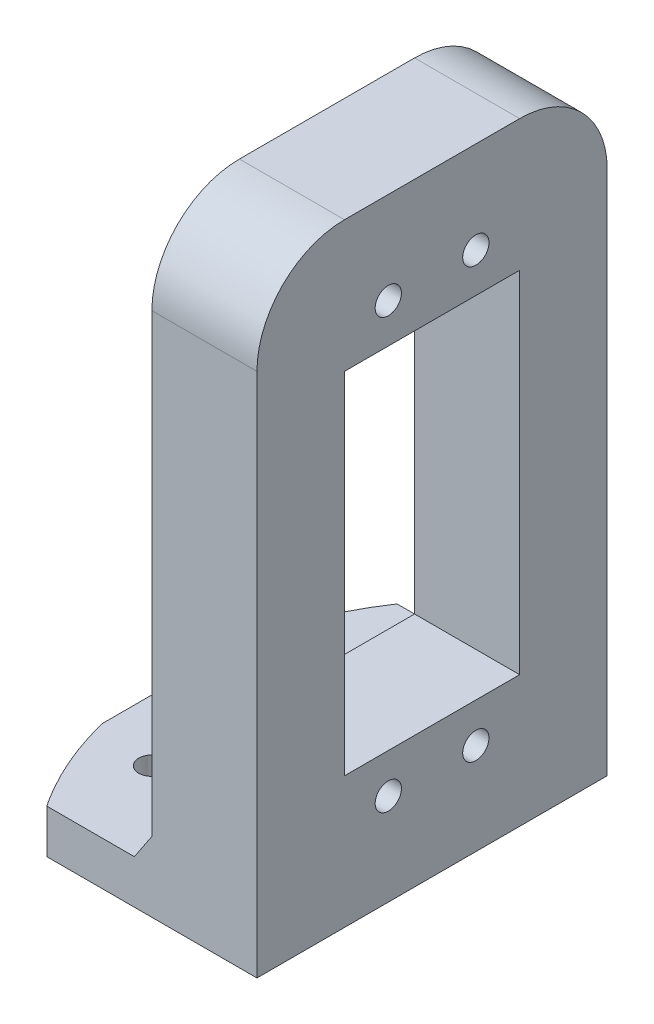
SolidWorks part; units mm, degrees
ref_plane "Front Plane" through (0, 0, 0) normal (0, 0, 1) x (1, 0, 0)
ref_plane "Top Plane" through (0, 0, 0) normal (0, 1, 0) x (1, 0, 0)
ref_plane "Right Plane" through (0, 0, 0) normal (1, 0, 0) x (0, 0, -1)
sketch "Sketch1" plane through (0, 0, 0) normal (1, 0, 0) x (0, 0, -1)
  line L1 (-20, 35) -> (20, 35)
  line L2 (-20, 35) -> (-20, -35)
  line L3 (-20, -35) -> (20, -35)
  line L4 (20, 35) -> (20, -35)
  line L5 (-20, 35) -> (20, -35) construction
  line L6 (-20, -35) -> (20, 35) construction
  point P0 (0, 0)
  dimension "D1" = 40
  dimension "D2" = 70
extrude "Boss-Extrude2" add sketch "Sketch1" along normal blind 9
sketch "Sketch3" plane through (0, 0, 0) normal (-1, 0, 0) x (0, 0, 1)
  line L1 (-10, 20) -> (10, 20)
  line L2 (-10, 20) -> (-10, -20)
  line L3 (-10, -20) -> (10, -20)
  line L4 (10, 20) -> (10, -20)
  line L5 (-10, 20) -> (10, -20) construction
  line L6 (-10, -20) -> (10, 20) construction
  point P0 (0, 0)
  dimension "D1" = 20
  dimension "D2" = 40
extrude "Cut-Extrude1" cut sketch "Sketch3" against normal through all
sketch "Sketch4" plane through (9, 0, 0) normal (1, 0, 0) x (0, 0, -1)
  line L0 (-20, 35) -> (-20, -35) construction
  line L1 (-10, 20) -> (10, 20) construction
  line L2 (10, -20) -> (-10, -20) construction
  circle A0 centre (-5, -24.5) radius 1.5
  circle A1 centre (5, -24.5) radius 1.5
  circle A2 centre (-5, 24.5) radius 1.5
  circle A3 centre (5, 24.5) radius 1.5
  point P0 (-5, 24.5)
  point P3 (5, 24.5)
  point P6 (-5, -24.5)
  point P7 (5, -24.5)
  dimension "D7" = 3
  dimension "D8" = 3
  dimension "D9" = 3
  dimension "D10" = 3
  dimension "D1" = 15
  dimension "D2" = 10
  dimension "D3" = 4.5
  dimension "D4" = 4.5
  dimension "D5" = 4.5
  dimension "D6" = 4.5
extrude "Cut-Extrude2" cut sketch "Sketch4" against normal through all
sketch "Sketch6" plane through (0, 0, 0) normal (-1, 0, 0) x (0, 0, 1)
  line L0 (20, 35) -> (20, -35) construction
  line L1 (-20, -35) -> (20, -35)
  line L2 (-20, -35) -> (-20, -30)
  line L3 (-20, -30) -> (20, -30)
  line L4 (20, -35) -> (20, -30)
  dimension "D1" = 5
extrude "Boss-Extrude3" add sketch "Sketch6" along normal blind 15
sketch "Sketch7" plane through (9, 0, 0) normal (1, 0, 0) x (0, 0, -1)
  line L0 (-20, 35) -> (-20, -35) construction
  line L1 (20, 35) -> (-20, 35) construction
  line L2 (-20, 25) -> (-20, 35)
  line L3 (-20, 35) -> (-10, 35)
  line L4 (20, -35) -> (20, 35) construction
  line L5 (10, 35) -> (20, 35)
  line L6 (20, 35) -> (20, 25)
  arc A0 (-10, 35) -> (-20, 25) centre (-10, 25) ccw
  arc A1 (20, 25) -> (10, 35) centre (10, 25) ccw
  point P0 (-20, 25)
  point P1 (-10, 35)
  point P8 (10, 35)
  point P12 (20, 25)
  dimension "D1" = 10
  dimension "D2" = 10
  dimension "D3" = 10
  dimension "D4" = 10
extrude "Cut-Extrude3" cut sketch "Sketch7" against normal through all
sketch "Sketch8" plane through (0, 0, -20) normal (0, 0, -1) x (-1, 0, 0)
  line L0 (0, -30) -> (0, 25) construction
  line L1 (15, -30) -> (0, -30) construction
  line L2 (0, -27) -> (5, -30)
  line L3 (0, -27) -> (0, -30)
  line L4 (0, -30) -> (5, -30)
  point P0 (0, -27)
  point P1 (5, -30)
  dimension "D1" = 3
  dimension "D2" = 5
extrude "Boss-Extrude4" add sketch "Sketch8" against normal blind 40
sketch "Sketch9" plane through (-15, 0, 0) normal (-1, 0, 0) x (0, 0, 1)
  line L1 (-20, -30) -> (20, -30)
  line L2 (-20, -30) -> (-20, -35)
  line L3 (-20, -35) -> (20, -35)
  line L4 (20, -30) -> (20, -35)
extrude "Boss-Extrude5" add sketch "Sketch9" along normal blind 5
sketch "Sketch10" plane through (0, -30, 0) normal (0, 1, 0) x (1, 0, 0)
  line L0 (-20, -20) -> (-20, 20) construction
  line L1 (-20, 20) -> (-5, 20) construction
  line L2 (-20, -20) -> (-5, -20) construction
  circle A0 centre (-13, 10) radius 1.5
  circle A1 centre (-13, -10) radius 1.5
  point P0 (-13, 10)
  point P1 (-13, -10)
  dimension "D5" = 3
  dimension "D6" = 3
  dimension "D1" = 7
  dimension "D2" = 7
  dimension "D3" = 10
  dimension "D4" = 10
extrude "Cut-Extrude4" cut sketch "Sketch10" against normal through all
sketch "Sketch11" plane through (0, -30, 0) normal (0, 1, 0) x (1, 0, 0)
  line L0 (-20, 20) -> (-5, 20) construction
  line L1 (-20, -20) -> (-20, 20) construction
  line L2 (-20, -20) -> (-5, -20) construction
  line L5 (-15, 20) -> (-23.0603, 8.003) construction
  line L6 (-23.0603, 8.003) -> (-23.0603, -7.997) construction
  line L8 (-23.0603, -7.997) -> (-15, -20) construction
  line L9 (-15, 20) -> (-20, 20)
  line L10 (-20, 20) -> (-20, -20)
  line L11 (-20, -20) -> (-15, -20)
  spline S0 degree 3 poles (-15, 20) (-23.0603, 8.003) (-23.0603, -7.997) (-15, -20) knots 0 0 0 0 1 1 1 1
  point P0 (-15, 20)
  point P1 (-20, 8)
  point P4 (-15, -20)
  point P7 (-20, -8)
  line M3 (-20, -20) -> (-5, -20)
  line M5 (-5, 20) -> (-20, 20)
  line M6 (-20, 20) -> (-20, -20)
  dimension "D1" = 5
  dimension "D2" = 12
  dimension "D3" = 12
  dimension "D4" = 5
extrude "Cut-Extrude5" cut sketch "Sketch11" against normal through all contours S0 M5 M6 | S0 M6 M3 region at (-18.4537, -30, -16.5606) region at (-18.4536, -30, 16.5593)
sketch "Sketch12" plane through (0, 0, 0) normal (-1, 0, 0) x (0, 0, 1)
  line L0 (-20, -27) -> (-20, 25) construction
  line L1 (-10, 35) -> (10, 35)
  line L2 (20, 25) -> (20, -27)
  line L3 (20, -27) -> (-20, -27)
  line L4 (-20, -27) -> (-20, 25)
  line L5 (-10, 20) -> (10, 20)
  line L6 (10, 20) -> (10, -20)
  line L7 (10, -20) -> (-10, -20)
  line L8 (-10, -20) -> (-10, 20)
  arc A0 (-10, 35) -> (-20, 25) centre (-10, 25) ccw construction
  arc A1 (-10, 35) -> (-20, 25) centre (-10, 25) ccw
  arc A2 (20, 25) -> (10, 35) centre (10, 25) ccw
  circle A3 centre (-5, 24.5) radius 1.5
  circle A4 centre (5, 24.5) radius 1.5
  circle A5 centre (5, -24.5) radius 1.5
  circle A6 centre (-5, -24.5) radius 1.5
  spline S0 degree 1 poles (-20, -27) (-20, 25) knots 0 0 1 1
  line M1 (-10, 20) -> (10, 20)
  line M2 (10, 20) -> (10, -20)
  line M3 (10, -20) -> (-10, -20)
  line M4 (-10, -20) -> (-10, 20)
  circle M5 centre (5, -24.5) radius 1.5
  circle M6 centre (-5, 24.5) radius 1.5
  circle M7 centre (5, 24.5) radius 1.5
  circle M8 centre (-5, -24.5) radius 1.5
  line M9 (-20, 25) -> (-20, -27)
  line M10 (-20, -27) -> (20, -27)
  line M11 (20, -27) -> (20, 25)
  arc M12 (20, 25) -> (10, 35) centre (10, 25) ccw
  line M13 (10, 35) -> (-10, 35)
  arc M14 (-10, 35) -> (-20, 25) centre (-10, 25) ccw
extrude "Boss-Extrude6" add sketch "Sketch12" along normal blind 3 contours M14 M9 M10 M11 M12 M13 M6 M8 M7 M5 M4 M1 M2 M3 region at (0, 34.2622, 0)
sketch "Sketch13" plane through (0, 0, -20) normal (0, 0, -1) x (-1, 0, 0)
  line L0 (3, -27) -> (5, -30)
  line L1 (5, -30) -> (0, -27)
  line L2 (0, -27) -> (3, -27)
extrude "Boss-Extrude7" add sketch "Sketch13" against normal blind 40
